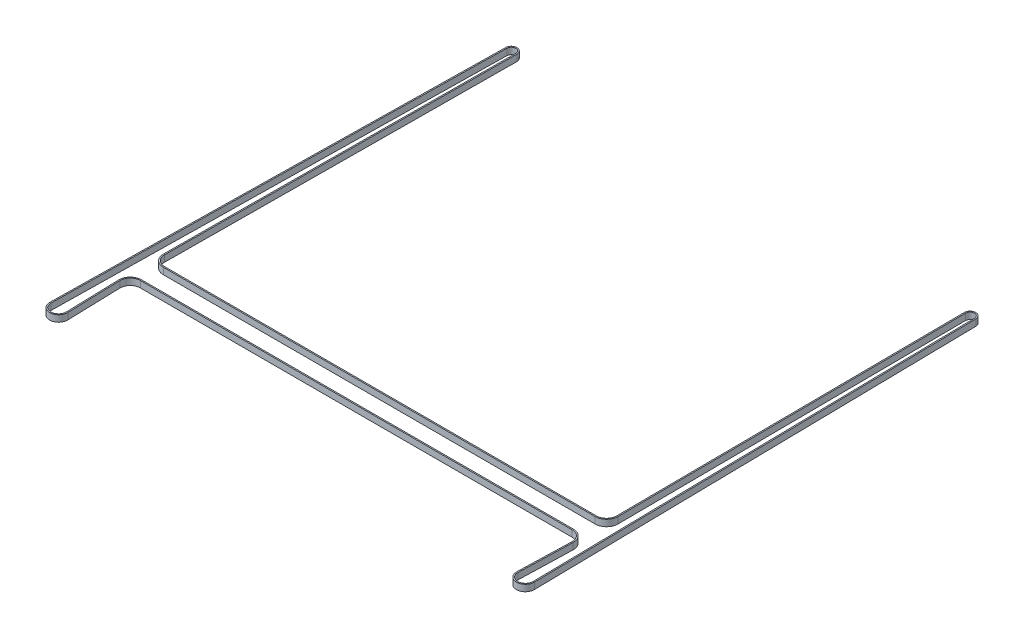
SolidWorks part; units mm, degrees
ref_plane "Front Plane" through (0, 0, 0) normal (0, 0, 1) x (1, 0, 0)
ref_plane "Top Plane" through (0, 0, 0) normal (0, 1, 0) x (1, 0, 0)
ref_plane "Right Plane" through (0, 0, 0) normal (1, 0, 0) x (0, 0, -1)
ref_plane "Plane1" through (0, 98.1376, 0) normal (0, 1, 0) x (1, 0, 0)
sketch "Sketch1" plane through (0, 0, 0) normal (0, 1, 0) x (1, 0, 0)
  line L0 (476.8725, -81.4029) -> (484.0318, -521.5921)
  line L1 (466.5367, -521.4767) -> (468.0857, -468.8972)
  line L2 (465.749, -81.5313) -> (468.0898, -424.9143)
  line L3 (458.14, -458.6542) -> (217.9548, -458.6542)
  line L4 (34.32, -434.9322) -> (260.3066, -434.9322)
  line L5 (246.23, -12.3063) -> (246.23, 12.3063) construction
  line L6 (246.23, -327.9877) -> (246.23, -29.8379) construction
  line L7 (25.9233, -521.4767) -> (24.3743, -468.8972)
  line L8 (15.5875, -81.4029) -> (8.4282, -521.5921)
  line L9 (26.711, -81.5313) -> (24.3702, -424.9143)
  line L10 (34.32, -458.6542) -> (217.9548, -458.6542)
  line L11 (458.14, -434.9322) -> (260.3066, -434.9322)
  circle A1 centre (475.2829, -521.7344) radius 8.75 construction
  circle A2 centre (458.14, -468.6042) radius 8.75 construction
  circle A3 centre (458.14, -468.6042) radius 8.75 construction
  circle A4 centre (475.2829, -521.7344) radius 8.75
  circle A5 centre (458.14, -424.9822) radius 8.75 construction
  arc A6 (466.6098, -84.3778) -> (467.5641, -85.5151) centre (471.31, -81.4029) ccw construction
  circle A7 centre (471.31, -81.4029) radius 5.5625 construction
  arc A8 (484.0318, -521.5921) -> (466.5367, -521.4767) centre (475.2829, -521.7344) cw
  arc A9 (468.0857, -468.8972) -> (458.14, -458.6542) centre (458.14, -468.6042) ccw
  arc A10 (476.8725, -81.4029) -> (465.749, -81.5313) centre (471.311, -81.4934) ccw
  arc A11 (468.0898, -424.9143) -> (458.14, -434.9322) centre (458.14, -424.9822) cw
  circle A14 centre (34.32, -468.6042) radius 9.95 construction
  arc A15 (8.4282, -521.5921) -> (25.9233, -521.4767) centre (17.1771, -521.7344) ccw
  arc A16 (15.5875, -81.4029) -> (26.711, -81.5313) centre (21.149, -81.4934) cw
  arc A17 (24.3702, -424.9143) -> (34.32, -434.9322) centre (34.32, -424.9822) ccw
  arc A18 (24.3743, -468.8972) -> (34.32, -458.6542) centre (34.32, -468.6042) cw
  circle A19 centre (471.31, -81.4029) radius 8 construction
  circle A20 centre (471.31, -81.4029) radius 8
  circle A21 centre (471.31, -81.4029) radius 8 construction
  circle A22 centre (471.31, -81.4029) radius 8
  circle A23 centre (458.14, -424.9822) radius 8.75 construction
  dimension "D2" = 1.2
  dimension "D1" = 1.2
  dimension "D3" = 0
extrude "Extrude-Thin1" add sketch "Sketch1" along normal blind 6.35 from surface thin contours L11 L4 A17 L9 A16 L8 A15 L7 A18 L10 L3 A9 L1 A8 L0 A10 L2 A11 starting at plane "Plane1" thin type one direction reverse wall 1.2
